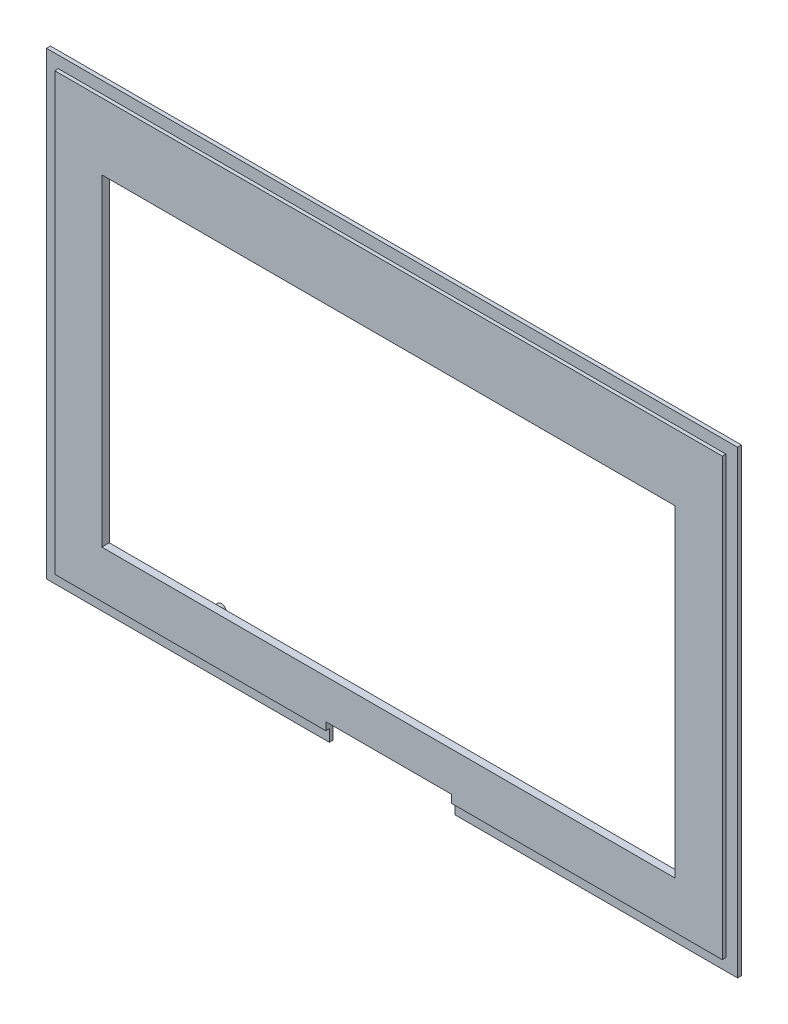
SolidWorks part; units mm, degrees
ref_plane "Plano frontal" through (0, 0, 0) normal (0, 0, 1) x (1, 0, 0)
ref_plane "Plano superior" through (0, 0, 0) normal (0, 1, 0) x (1, 0, 0)
ref_plane "Plano direito" through (0, 0, 0) normal (1, 0, 0) x (0, 0, -1)
sketch "Esboço1" plane through (0, 0, 0) normal (0, 0, 1) x (1, 0, 0)
  line L0 (11, 65.5) -> (171, 65.5) construction
  line L1 (0, 0) -> (182, 0)
  line L2 (0, 0) -> (0, 131)
  line L3 (0, 131) -> (182, 131)
  line L4 (182, 0) -> (182, 131)
  line L5 (11, 113.5) -> (171, 113.5)
  line L6 (11, 113.5) -> (11, 17.5)
  line L7 (11, 17.5) -> (171, 17.5)
  line L8 (171, 113.5) -> (171, 17.5)
  line L9 (5.7, 118.4) -> (176.3, 118.4)
  line L10 (5.7, 118.4) -> (5.7, 6.8)
  line L11 (5.7, 6.8) -> (176.3, 6.8)
  line L12 (176.3, 118.4) -> (176.3, 6.8)
  line L13 (5.9, 118.2) -> (176.1, 118.2)
  line L14 (5.9, 118.2) -> (5.9, 7)
  line L15 (5.9, 7) -> (176.1, 7)
  line L16 (176.1, 118.2) -> (176.1, 7)
  line L17 (91, 131) -> (91, 0) construction
  point P21 (91, 65.5)
  point P22 (91, 65.5)
  dimension "D1" = 131
  dimension "D2" = 182
  dimension "D3" = 160
  dimension "D4" = 96
  dimension "D5" = 170.2
  dimension "D6" = 111.2
  dimension "D7" = 0.2
  dimension "D8" = 4.7
  dimension "D9" = 0.2
  dimension "D10" = 0.2
  dimension "D11" = 0.2
  dimension "D12" = 5.1
  dimension "D13" = 5.1
  dimension "D14" = 10.5
extrude "Ressalto-extrusão1" add sketch "Esboço1" along normal blind 0.9 contours L16 L15 L14 L13
sketch "Esboço4" plane through (0, 0, 0) normal (0, 0, -1) x (-1, 0, 0)
  line L1 (-179.1, 121.2) -> (-2.9, 121.2)
  line L2 (-179.1, 121.2) -> (-179.1, 4)
  line L3 (-179.1, 4) -> (-2.9, 4)
  line L4 (-2.9, 121.2) -> (-2.9, 4)
  line L8 (-176.1, 118.2) -> (-176.1, 7) construction
  line L9 (-5.9, 118.2) -> (-176.1, 118.2) construction
  line L10 (-5.9, 7) -> (-176.1, 7) construction
  line L11 (-5.9, 118.2) -> (-5.9, 7) construction
  dimension "D1" = 3
  dimension "D2" = 3
  dimension "D3" = 3
  dimension "D4" = 3
extrude "Ressalto-extrusão3" add sketch "Esboço4" along normal blind 1
sketch "Esboço5" plane through (0, 4, 0) normal (0, -1, 0) x (1, 0, 0)
  line L0 (179.1, -1) -> (2.9, -1) construction
  line L1 (75, -1) -> (107, -1)
  line L2 (75, -1) -> (75, 0.9)
  line L3 (75, 0.9) -> (107, 0.9)
  line L4 (107, -1) -> (107, 0.9)
  line L5 (5.9, 0.9) -> (176.1, 0.9) construction
  point P8 (91, -1)
  point P9 (91, -1)
  dimension "D1" = 32
extrude "Corte-extrusão3" cut sketch "Esboço5" against normal blind 5
sketch "Esboço6" plane through (0, 0, -1) normal (0, 0, -1) x (-1, 0, 0)
  line L0 (-43.3, 106.45) -> (-42.05, 106.45) construction
  line L1 (-44, 16.15) -> (-44, 14.9) construction
  line L2 (-110.15, 109) -> (-40.75, 109) construction
  line L3 (-110.15, 109) -> (-110.15, 8.4) construction
  line L4 (-110.15, 8.4) -> (-40.75, 8.4) construction
  line L5 (-40.75, 109) -> (-40.75, 8.4) construction
  line L6 (-44, 16.15) -> (-42.75, 16.15) construction
  line L7 (-43.3, 106.45) -> (-43.3, 107.7) construction
  line L8 (-108.3, 106.45) -> (-108.3, 107.7) construction
  line L9 (-108.3, 106.45) -> (-109.55, 106.45) construction
  line L10 (-108.3, 14.75) -> (-108.3, 13.5) construction
  line L11 (-108.3, 14.75) -> (-109.55, 14.75) construction
  line L12 (-75, 9) -> (-107, 9) construction
  line L13 (-108.3, 14.75) -> (-108.3, 16) construction
  circle A0 centre (-108.3, 14.75) radius 1.25
  circle A1 centre (-108.3, 106.45) radius 1.25
  circle A2 centre (-43.3, 106.45) radius 1.25
  circle A3 centre (-44, 16.15) radius 1.25
  point P22 (-91, 9)
  dimension "D1" = 2.5
  dimension "D2" = 2.5
  dimension "D3" = 2.5
  dimension "D4" = 2.5
  dimension "D5" = 100.6
  dimension "D6" = 69.4
  dimension "D7" = 6.5
  dimension "D8" = 2
  dimension "D9" = 1.3
  dimension "D10" = 1.3
  dimension "D11" = 2.6
  dimension "D12" = 0.6
  dimension "D13" = 0.6
  dimension "D14" = 5.1
  dimension "D15" = 19.15
  dimension "D16" = 9
extrude "Ressalto-extrusão4" add sketch "Esboço6" along normal blind 2.5
sketch "Esboço10" plane through (0, 0, -1) normal (0, 0, -1) x (-1, 0, 0)
  line L0 (-108.3, 106.45) -> (-107.05, 106.45) construction
  line L1 (-58.55, 108.45) -> (-45.55, 108.45)
  line L2 (-58.55, 108.45) -> (-58.55, 104.45)
  line L3 (-58.55, 104.45) -> (-45.55, 104.45)
  line L4 (-45.55, 108.45) -> (-45.55, 104.45)
  line L5 (-43.3, 106.45) -> (-44.55, 106.45) construction
  circle A0 centre (-108.3, 106.45) radius 1.25 construction
  circle A1 centre (-43.3, 106.45) radius 1.25 construction
  point P9 (-58.55, 106.45)
  point P15 (0, 0)
  dimension "D1" = 1
  dimension "D2" = 14
  dimension "D3" = 4
extrude "Corte-extrusão6" cut sketch "Esboço10" against normal blind 1.1
sketch "Esboço12" plane through (0, 0, 0.9) normal (0, 0, 1) x (1, 0, 0)
  line L0 (5.9, 118.2) -> (5.9, 7) construction
  line L1 (17.9, 101.2) -> (164.1, 101.2)
  line L2 (17.9, 101.2) -> (17.9, 19)
  line L3 (17.9, 19) -> (164.1, 19)
  line L4 (164.1, 101.2) -> (164.1, 19)
  line L5 (5.9, 7) -> (75, 7) construction
  line L6 (176.1, 118.2) -> (176.1, 7) construction
  line L7 (5.9, 118.2) -> (176.1, 118.2) construction
  dimension "D1" = 12
  dimension "D2" = 12
  dimension "D3" = 12
  dimension "D4" = 17
extrude "Corte-extrusão8" cut sketch "Esboço12" against normal blind 10
